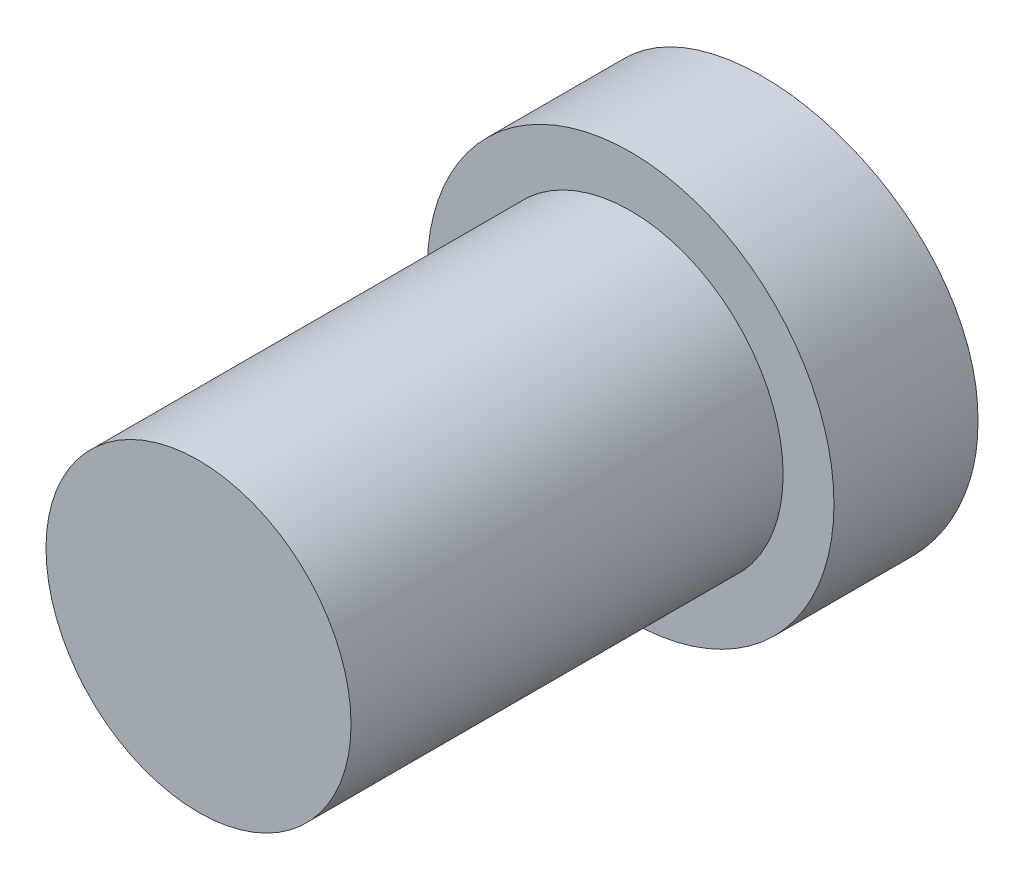
SolidWorks part; units mm, degrees
ref_plane "Front Plane" through (0, 0, 0) normal (0, 0, 1) x (1, 0, 0)
ref_plane "Top Plane" through (0, 0, 0) normal (0, 1, 0) x (1, 0, 0)
ref_plane "Right Plane" through (0, 0, 0) normal (1, 0, 0) x (0, 0, -1)
sketch "Sketch1" plane through (0, 0, 0) normal (0, 0, 1) x (1, 0, 0)
  circle A0 centre (0, 0) radius 4.5
  circle A1 centre (0, 0) radius 6
  dimension "D1" = 12
  dimension "D2" = 9
extrude "Boss-Extrude1" add sketch "Sketch1" along normal blind 17 contours A0 region at (0, 0, 0)
extrude "Boss-Extrude2" add sketch "Sketch1<3>" along normal blind 4.25
sketch "Sketch1<3>" plane through (0, 0, 0) normal (0, 0, 1) x (1, 0, 0) same geometry as "Sketch1"
sketch "Sketch2" plane through (0, 0, 0) normal (1, 0, 0) x (0, 0, -1)
  line L0 (0, 6) -> (-4.25, 6) construction
  line L1 (-4.25, -6) -> (0, -6) construction
  line L2 (-0.37, 6) -> (0, 6)
  line L3 (0, 6) -> (0, -6)
  line L4 (0, -6) -> (-0.37, -6)
  arc A0 (-0.37, 6) -> (-0.37, -6) centre (-47.8726, 0) cw
  dimension "D2" = 47.88
  dimension "D1" = 0.37
extrude "Cut-Extrude1" cut sketch "Sketch2" against normal through all both and the other way through all contours L2 A0 L3 | L3 A0 L4 | A0 L4 L3 L2 region at (0, -4.5705, 0.1119) region at (0, 4.5705, 0.1119)
